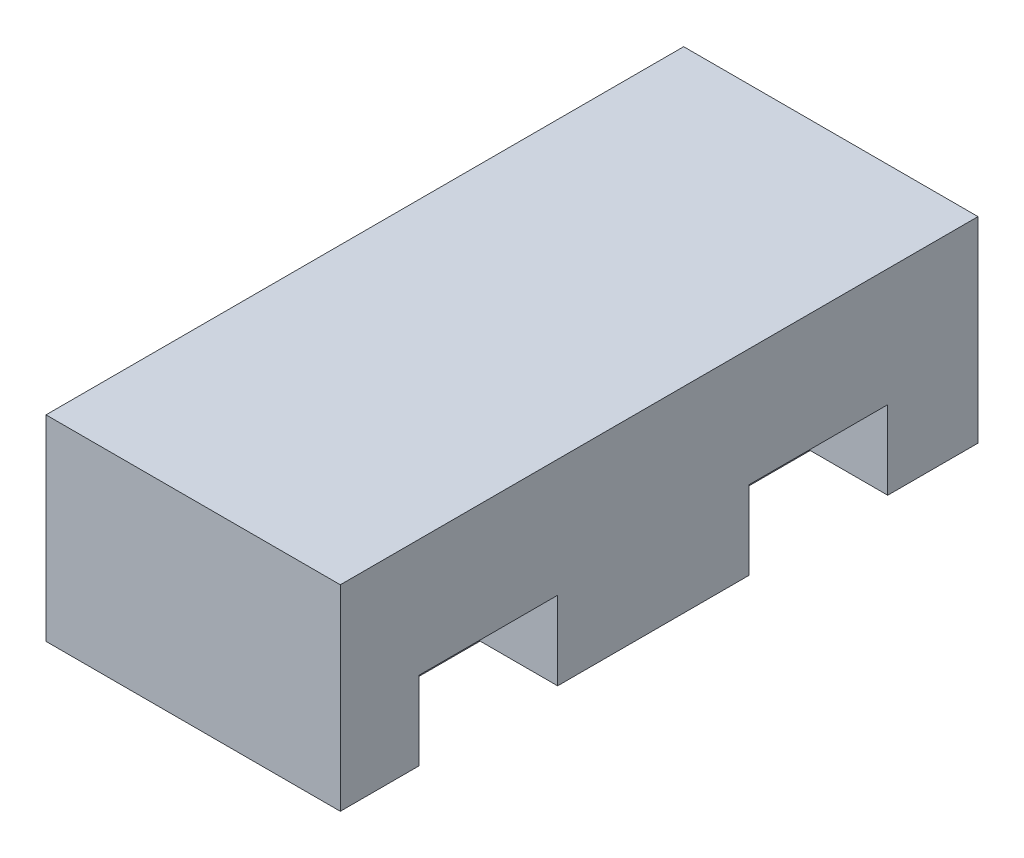
SolidWorks part; units mm, degrees
other "标注1"
sketch "草图3" plane through (-22.25, 4, -10) normal (-0.231, 0.6469, -0.7268) x (-0.9696, -0.2151, 0.1167)
ref_plane "前视基准面" through (0, 0, 0) normal (0, 0, 1) x (1, 0, 0)
ref_plane "上视基准面" through (0, 0, 0) normal (0, 1, 0) x (1, 0, 0)
ref_plane "右视基准面" through (0, 0, 0) normal (1, 0, 0) x (0, 0, -1)
other "Configuration Table"
sketch "草图4" plane through (0, 0, 0) normal (0, 1, 0) x (1, 0, 0)
  line L1 (-15, -32.5) -> (15, -32.5)
  line L2 (-15, -32.5) -> (-15, 32.5)
  line L3 (-15, 32.5) -> (15, 32.5)
  line L4 (15, -32.5) -> (15, 32.5)
  line L5 (-15, -32.5) -> (15, 32.5) construction
  line L6 (-15, 32.5) -> (15, -32.5) construction
  point P0 (0, 0)
  point P6 (33.0323, 4.0633)
  dimension "D1" = 30
  dimension "D2" = 65
extrude "凸台-拉伸1" add sketch "草图4" along normal blind 20 contours L1 L4 L3 L2
sketch "草图5" plane through (0, 0, 0) normal (0, -1, 0) x (-1, 0, 0)
  line L0 (0, -24.5) -> (0, 23.3) construction
  line L1 (7.1, -24.5) -> (-7.1, -24.5)
  line L2 (7.1, -24.5) -> (7.1, 23.3)
  line L3 (7.1, 23.3) -> (-7.1, 23.3)
  line L4 (-7.1, -24.5) -> (-7.1, 23.3)
  line L5 (15, -32.5) -> (-15, -32.5) construction
  line L6 (15, 32.5) -> (-15, 32.5) construction
  line L7 (3.4011, -24.5) -> (3.4011, -10.35) construction
  line L8 (15, -10.35) -> (-15, -10.35)
  line L9 (15, -10.35) -> (15, 9.15)
  line L10 (15, 9.15) -> (-15, 9.15)
  line L11 (-15, -10.35) -> (-15, 9.15)
  line L12 (3.4011, 9.15) -> (3.4011, 23.3) construction
  line L13 (15, -32.5) -> (15, 32.5) construction
  line L14 (-15, -32.5) -> (-15, 32.5) construction
  line L15 (7.1, -24.5) -> (15, -24.5)
  line L16 (15, -24.5) -> (15, -10.35)
  line L17 (-7.1, -24.5) -> (-15, -24.5)
  line L18 (-15, -24.5) -> (-15, -10.35)
  line L19 (-7.1, 23.3) -> (-15, 23.3)
  line L20 (-15, 23.3) -> (-15, 9.15)
  line L21 (7.1, 23.3) -> (15, 23.3)
  line L22 (15, 23.3) -> (15, 9.15)
  line M9 (15, -32.5) -> (15, 32.5)
  line M11 (-15, 32.5) -> (-15, -32.5)
  dimension "D1" = 14.2
  dimension "D2" = 8
  dimension "D3" = 9.2
  dimension "D4" = 19.5
extrude "切除-拉伸1" cut sketch "草图5" against normal blind 8 contours L2 L15 L8 M9 | L21 L2 L10 M9 | L4 L19 L10 M11 | L17 L4 L8 M11 region at (-11.05, 0, 17.425) region at (11.05, 0, 17.425) region at (-11.05, 0, -16.225) region at (11.05, 0, -16.225)
